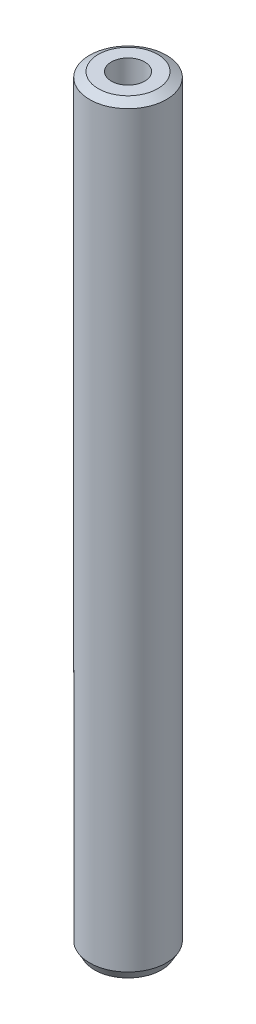
SolidWorks part; units mm, degrees
ref_plane "Front Plane" through (0, 0, 0) normal (0, 0, 1) x (1, 0, 0)
ref_plane "Top Plane" through (0, 0, 0) normal (0, 1, 0) x (1, 0, 0)
ref_plane "Right Plane" through (0, 0, 0) normal (1, 0, 0) x (0, 0, -1)
sketch "Sketch1" plane through (0, 0, 0) normal (0, 1, 0) x (1, 0, 0)
  circle A0 centre (0, 0) radius 20
  dimension "SHAFT_OD" = 40
extrude "Boss-Extrude1" add sketch "Sketch1" along normal blind 396.2824
sketch "Sketch2" plane through (0, 0, 0) normal (0, 1, 0) x (1, 0, 0)
  circle A0 centre (0, 0) radius 8.6749
  dimension "BORE_D" = 17.3498
extrude "Cut-Extrude1" cut sketch "Sketch2" along normal through all
chamfer "Chamfer1" distance 2.6164 angle 60 2 edges at (0, 396.2824, 20) (0, 0, 20) first distance on face at (0, 396.2824, 20) first distance on face at (0, 0, 8.6749)
